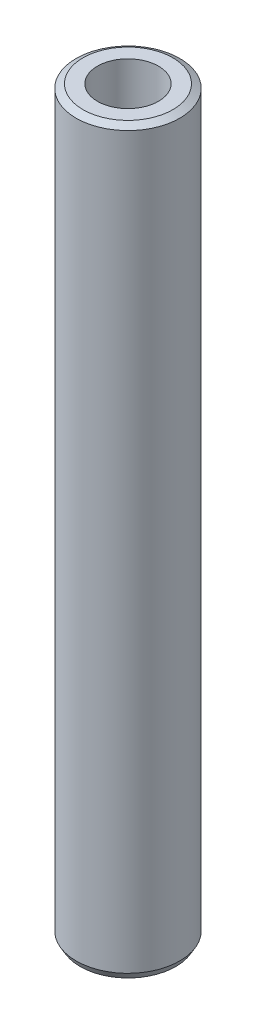
SolidWorks part; units mm, degrees
ref_plane "Front Plane" through (0, 0, 0) normal (0, 0, 1) x (1, 0, 0)
ref_plane "Top Plane" through (0, 0, 0) normal (0, 1, 0) x (1, 0, 0)
ref_plane "Right Plane" through (0, 0, 0) normal (1, 0, 0) x (0, 0, -1)
sketch "Sketch1" plane through (0, 0, 0) normal (0, 1, 0) x (1, 0, 0)
  circle A0 centre (0, 0) radius 27.5
  dimension "SHAFT_OD" = 55
extrude "Boss-Extrude1" add sketch "Sketch1" along normal blind 393.137
sketch "Sketch2" plane through (0, 0, 0) normal (0, 1, 0) x (1, 0, 0)
  circle A0 centre (0, 0) radius 16.2015
  dimension "BORE_D" = 32.403
extrude "Cut-Extrude1" cut sketch "Sketch2" along normal through all
chamfer "Chamfer1" distance 2.1052 angle 60 2 edges at (0, 393.137, 27.5) (0, 0, 27.5) first distance on face at (0, 393.137, 27.5) first distance on face at (0, 0, 16.2015)
